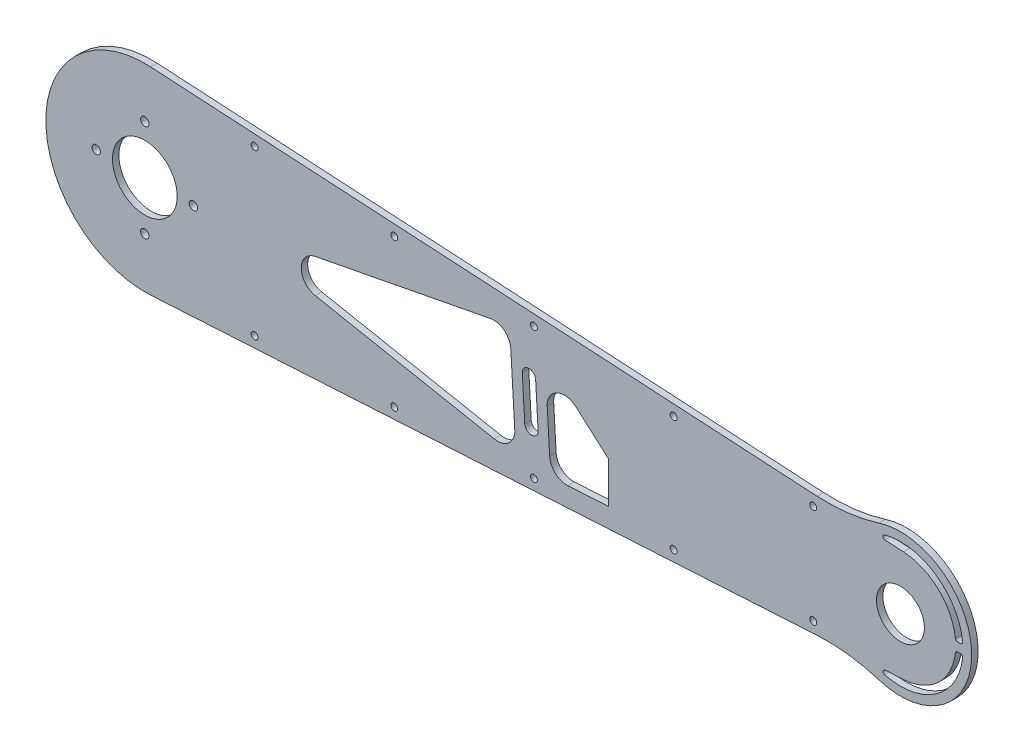
SolidWorks part; units mm, degrees
material "Thornel VCB-20 Carbon Cloth"
ref_plane "Front Plane" through (0, 0, 0) normal (0, 0, 1) x (1, 0, 0)
ref_plane "Top Plane" through (0, 0, 0) normal (0, 1, 0) x (1, 0, 0)
ref_plane "Right Plane" through (0, 0, 0) normal (1, 0, 0) x (0, 0, -1)
sketch "Sketch1" plane through (0, 0, 0) normal (0, 0, 1) x (1, 0, 0)
  line L0 (-175, 0) -> (175, 0) construction
  line L1 (-172.3519, 45.7735) -> (176.4806, 25.5923)
  line L2 (-172.3519, -45.7735) -> (176.4806, -25.5923)
  line L3 (134.6298, 23.0052) -> (-124.15, 37.9765) construction
  line L4 (-59.4551, -34.2336) -> (5.2399, -30.4908) construction
  line L5 (-129.15, 0) -> (-129.15, 62.9978) construction
  line L6 (139.694, 0) -> (139.694, 19.7682) construction
  circle A0 centre (175, 0) radius 11.1125
  arc A1 (176.4806, 25.5923) -> (176.4806, -25.5923) centre (175, 0) cw
  circle A3 centre (-175, 0) radius 22.5 construction
  circle A7 centre (-175, 0) radius 15
  circle A8 centre (175, 0) radius 35.306 construction
  circle A9 centre (-124.15, 37.9765) radius 1.6
  circle A10 centre (-59.4551, 34.2336) radius 1.6
  circle A11 centre (5.2399, 30.4908) radius 1.6
  circle A12 centre (69.9348, 26.748) radius 1.6
  circle A13 centre (134.6298, 23.0052) radius 1.6
  circle A15 centre (134.6298, -23.0052) radius 1.6
  circle A16 centre (69.9348, -26.748) radius 1.6
  circle A17 centre (5.2399, -30.4908) radius 1.6
  circle A18 centre (-59.4551, -34.2336) radius 1.6
  circle A19 centre (-124.15, -37.9765) radius 1.6
  arc A20 (-172.3519, 45.7735) -> (-172.3519, -45.7735) centre (-175, 0) ccw
  point P4 (0, 0)
  point P18 (-175, 22.5)
  point P21 (-197.5, 0)
  point P22 (-175, -22.5)
  point P23 (-152.5, 0)
  dimension "D2" = 22.225
  dimension "D3" = 45.85
  dimension "D5" = 45
  dimension "D6" = 3.2
  dimension "D7" = 259.2125
  dimension "D8" = 5
  dimension "D10" = 30
  dimension "D11" = 70.612
  dimension "D16" = 5
  dimension "D1" = 350
  dimension "D12" = 5
extrude "Boss-Extrude1" add sketch "Sketch1" along normal blind 3
sketch "Sketch4" plane through (0, 0, 3) normal (0, 0, 1) x (1, 0, 0)
  point P10 (-197.5, 0)
  point P13 (-175, 22.5)
  point P16 (-152.5, 0)
  point P19 (-175, -22.5)
hole_wizard "M3.5 Clearance Hole1" positions "Sketch4" profile "Sketch6" hole size "M3.5" standard "ANSI Metric" end condition up to next
sketch "Sketch6" plane through (-197.5, 0, 3) normal (1, 0, 0) x (0, -1, 0)
  line L0 (0, 0) -> (0, 3)
  line L1 (0, 3) -> (1.95, 3)
  line L2 (1.95, 3) -> (1.95, 0)
  line L5 (1.95, 0) -> (0, 0)
  line L11 (0, -6.35) -> (0, 107.95) construction
  dimension "Thru Hole Dia." = 3.9
  dimension "Thru Hole Depth" = 3
sketch "Sketch7" plane through (0, 0, 3) normal (0, 0, 1) x (1, 0, 0)
  line L0 (69.9348, 26.748) -> (69.9348, -26.748) construction
  line L1 (69.9348, -26.748) -> (134.6298, 0) construction
  line L2 (134.6298, 0) -> (69.9348, 26.748) construction
  line L3 (134.6298, 0) -> (-152.5, 0) construction
  line L4 (134.6298, -23.0052) -> (134.6298, 23.0052) construction
  line L5 (50.7875, 31.4181) -> (108.8966, 7.393)
  line L6 (108.8966, -7.393) -> (50.7875, -31.4181)
  line L7 (39.7309, -24.0251) -> (39.7309, 24.0251)
  line L8 (5.2399, -30.4908) -> (1.4093, 35.7208) construction
  line L9 (5.2399, 30.4908) -> (69.9348, -26.748) construction
  line L10 (5.2399, 30.4908) -> (69.9348, 26.748) construction
  line L11 (5.2399, -30.4908) -> (69.9348, -26.748) construction
  line L12 (-152.5, 0) -> (-59.4551, 34.2336) construction
  line L13 (-59.4551, 34.2336) -> (5.2399, 30.4908) construction
  line L14 (5.2399, 30.4908) -> (-152.5, 0) construction
  line L15 (100.1388, -30.3705) -> (100.1388, 13.4434)
  line L16 (92.6008, 21.43) -> (39.615, 24.4954)
  line L17 (33.8519, 10.5172) -> (86.8377, -36.362)
  line L18 (24.6909, 7.9407) -> (45.4857, -10.4575)
  line L19 (40.6467, -24.4357) -> (20.9821, -25.5734)
  line L20 (12.5334, -18.0488) -> (11.4032, 1.4871)
  line L21 (176.4806, 25.5923) -> (-172.3519, 45.7735) construction
  line L22 (-172.3519, -45.7735) -> (176.4806, -25.5923) construction
  line L23 (-3.637, -15.5655) -> (-5.471, 16.1351)
  line L24 (-14.9759, 23.5276) -> (-96.058, 7.8546)
  line L25 (-96.058, -7.8546) -> (-13.1419, -23.8821)
  line L35 (-197.5, 0) -> (-59.4551, 34.2336) construction
  line L52 (-59.4551, -34.2336) -> (-175, -22.5) construction
  line L53 (-14.7283, -43.8014) -> (-59.5639, -39.2483) construction
  line L54 (-0.1485, -35.2305) -> (3.4925, -35.6003) construction
  line L55 (4.0907, -10.6274) -> (2.9356, 9.3392) construction
  line L56 (0.9959, -10.8064) -> (-0.1592, 9.1602)
  line L57 (7.1855, -10.4483) -> (6.0304, 9.5183)
  arc A0 (108.8966, 7.393) -> (108.8966, -7.393) centre (105.84, 0) cw
  arc A1 (50.7875, -31.4181) -> (39.7309, -24.0251) centre (47.7309, -24.0251) cw
  arc A2 (50.7875, 31.4181) -> (39.7309, 24.0251) centre (47.7309, 24.0251) ccw
  arc A3 (100.1388, 13.4434) -> (92.6008, 21.43) centre (92.1388, 13.4434) ccw
  arc A4 (39.615, 24.4954) -> (33.8519, 10.5172) centre (39.1529, 16.5088) ccw
  arc A5 (100.1388, -30.3705) -> (86.8377, -36.362) centre (92.1388, -30.3705) cw
  arc A6 (45.4857, -10.4575) -> (40.6467, -24.4357) centre (40.1847, -16.4491) cw
  arc A7 (20.9821, -25.5734) -> (12.5334, -18.0488) centre (20.5201, -17.5868) cw
  arc A8 (24.6909, 7.9407) -> (11.4032, 1.4871) centre (19.3899, 1.9491) ccw
  arc A9 (-3.637, -15.5655) -> (-13.1419, -23.8821) centre (-11.6236, -16.0275) cw
  arc A10 (-5.471, 16.1351) -> (-14.9759, 23.5276) centre (-13.4576, 15.673) ccw
  arc A11 (-96.058, 7.8546) -> (-96.058, -7.8546) centre (-94.5397, 0) ccw
  circle A30 centre (-175, 0) radius 15 construction
  circle A31 centre (-175, 0) radius 15 construction
  circle A32 centre (-175, 0) radius 22.5 construction
  circle A49 centre (5.2399, -30.4908) radius 1.6 construction
  circle A50 centre (5.2399, -30.4908) radius 1.6
  arc A56 (0.9959, -10.8064) -> (7.1855, -10.4483) centre (4.0907, -10.6274) ccw
  arc A57 (6.0304, 9.5183) -> (-0.1592, 9.1602) centre (2.9356, 9.3392) ccw
  point P36 (126.778, 0)
  point P59 (-136.6926, 0)
  point P102 (-14.7283, -43.8014)
  point P126 (3.5131, -0.6441)
  dimension "D8" = 8
  dimension "D12" = 5
  dimension "D20" = 3.1
  dimension "D1" = 3
  dimension "D3" = 8
  dimension "D4" = 8
  dimension "D5" = 8
  dimension "D6" = 16
  dimension "D7" = 6
  dimension "D14" = 5
  dimension "D16" = 24.8967
  dimension "D22" = 20
extrude "Cut-Extrude1" cut sketch "Sketch7" against normal blind 10 contours L57 A57 L56 A56 | L24 A11 L25 A9 L23 A10 | L18 A8 L20 A7 L19 A6 region at (24.8307, -9.4802, 3) region at (-44.0971, -0.1663, 3) region at (3.5131, -0.6441, 3)
sketch "Sketch9" plane through (0, 0, 3) normal (0, 0, 1) x (1, 0, 0)
  line L2 (176.4806, 25.5923) -> (-172.3519, 45.7735) construction
  line L3 (-172.3519, -45.7735) -> (176.4806, -25.5923) construction
  line L4 (254.5375, 0) -> (208, 0) construction
  line L5 (200.557, 2) -> (203.931, 2)
  line L6 (200.557, -2) -> (203.931, -2)
  line L7 (162.9445, 26.3755) -> (155.7345, 26.7926)
  line L8 (162.9445, -26.3755) -> (155.7345, -26.7926)
  arc A1 (155.7345, -26.7926) -> (155.7345, 26.7926) centre (175, 0) ccw
  arc A2 (176.4806, -25.5923) -> (176.4806, 25.5923) centre (175, 0) ccw construction
  arc A3 (200.557, -2) -> (200.557, 2) centre (175, 0) ccw
  arc A4 (162.9445, 26.3755) -> (203.931, 2) centre (175, 0) cw
  arc A5 (203.931, -2) -> (162.9445, -26.3755) centre (175, 0) cw
  dimension "D1" = 33
  dimension "D2" = 4
  dimension "D3" = 4
extrude "Boss-Extrude2" add sketch "Sketch9" against normal up to surface (3 mm away) up to face at (-38.6854, 0.0079, 0)
fillet "Fillet1" radius 1 6 edges at (162.9445, -26.3755, 1.5) (200.557, -2, 1.5) (203.931, -2, 1.5) (200.557, 2, 1.5) (203.931, 2, 1.5) (162.9445, 26.3755, 1.5)
fillet "Fillet2" radius 80 2 edges at (155.7345, 26.7926, 1.5) (155.7345, -26.7926, 1.5)
